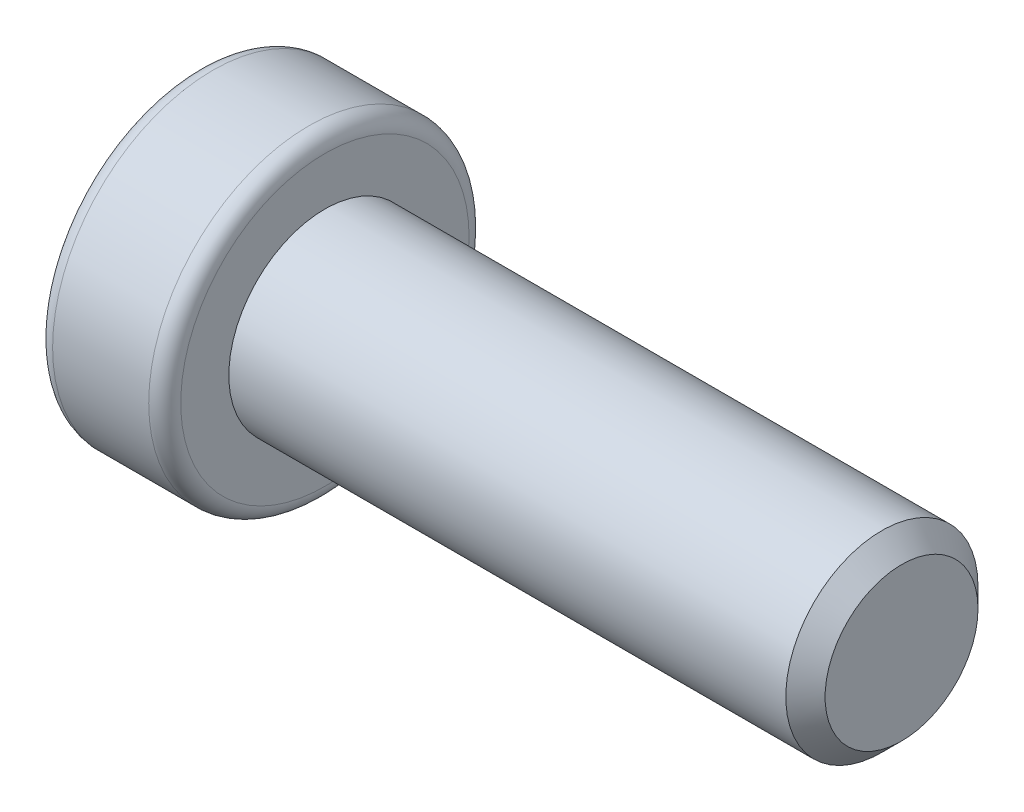
SolidWorks part; units mm, degrees
ref_plane "Front Plane" through (0, 0, 0) normal (0, 0, 1) x (1, 0, 0)
ref_plane "Top Plane" through (0, 0, 0) normal (0, 1, 0) x (1, 0, 0)
ref_plane "Right Plane" through (0, 0, 0) normal (1, 0, 0) x (0, 0, -1)
sketch "Sketch1" plane through (0, 0, 0) normal (0, 0, 1) x (1, 0, 0)
  line L0 (2.5, 0) -> (1, 1.5)
  line L1 (1, 1.5) -> (-0.5, 1.5)
  line L2 (-0.5, 1.5) -> (-1.5, 2.5)
  line L3 (-1.5, 2.5) -> (-3.6132, 2.5)
  line L4 (-3.6132, 2.5) -> (-4, 2.8868)
  line L5 (-4, 2.8868) -> (-4, 4.5)
  line L6 (-3.5, 5) -> (-0.5, 5)
  line L7 (0, 4.5) -> (0, 3)
  line L8 (0, 3) -> (17.3865, 3)
  line L9 (17.3865, 3) -> (18, 2.3865)
  line L10 (18, 2.3865) -> (18, 0)
  line L11 (18, 0) -> (2.5, 0)
  line L12 (18, 0) -> (2.5, 0) construction
  arc A0 (-4, 4.5) -> (-3.5, 5) centre (-3.5, 4.5) cw
  arc A1 (-0.5, 5) -> (0, 4.5) centre (-0.5, 4.5) cw
revolve "Revolve1" add sketch "Sketch1" angle 360 about L12
cosmetic thread "Cosmetic Thread1" parameters "D1"=12.5, "D2"=4.773
ref_plane "Plane1" through (-4, 0, 0) normal (1, 0, 0) x (0, 0, -1)
sketch "Sketch2" plane through (-4, 0, 0) normal (1, 0, 0) x (0, 0, -1)
  line L0 (-2.5, -1.4434) -> (0, -2.8868)
  line L1 (0, -2.8868) -> (2.5, -1.4434)
  line L2 (2.5, -1.4434) -> (2.5, 1.4434)
  line L3 (2.5, 1.4434) -> (0, 2.8868)
  line L4 (0, 2.8868) -> (-2.5, 1.4434)
  line L5 (-2.5, 1.4434) -> (-2.5, -1.4434)
extrude "Cut-Extrude1" cut sketch "Sketch2" along normal blind 2.5
ref_plane "Plane2" through (18, 0, 0) normal (1, 0, 0) x (0, 0, -1)
ref_plane "MONTAGE XY" through (0, 0, 0) normal (1, 0, 0) x (0, 0, -1)
ref_plane "MONTAGE XZ" through (0, 0, 0) normal (0, -1, 0) x (-1, 0, 0)
ref_plane "MONTAGE YZ" through (0, 0, 0) normal (0, 0, -1) x (-1, 0, 0)
ref_axis "MONTAGE X" through (0, 0, 80.9) along (0, 0, -1)
ref_axis "MONTAGE Y" through (0, -50, 0) along (0, 1, 0)
ref_axis "MONTAGE Z" through (80.9, 0, 0) along (-1, 0, 0)
sketch3d "MONTAGE"
  point P0 (0, 0, 0)
ref_plane "Schrauben_punkt XY" through (18, 0, 0) normal (-1, 0, 0) x (0, 0, 1)
ref_plane "Schrauben_punkt XZ" through (0, 0, 0) normal (0, 1, 0) x (1, 0, 0)
ref_plane "Schrauben_punkt YZ" through (0, 0, 0) normal (0, 0, -1) x (-1, 0, 0)
ref_axis "Schrauben_punkt X" through (18, 0, 80.9) along (0, 0, -1)
ref_axis "Schrauben_punkt Y" through (18, 50, 0) along (0, -1, 0)
ref_axis "Schrauben_punkt Z" through (-80.9, 0, 0) along (1, 0, 0)
sketch3d "Schrauben_punkt"
  point P0 (18, 0, 0)
other "Freeze***"
